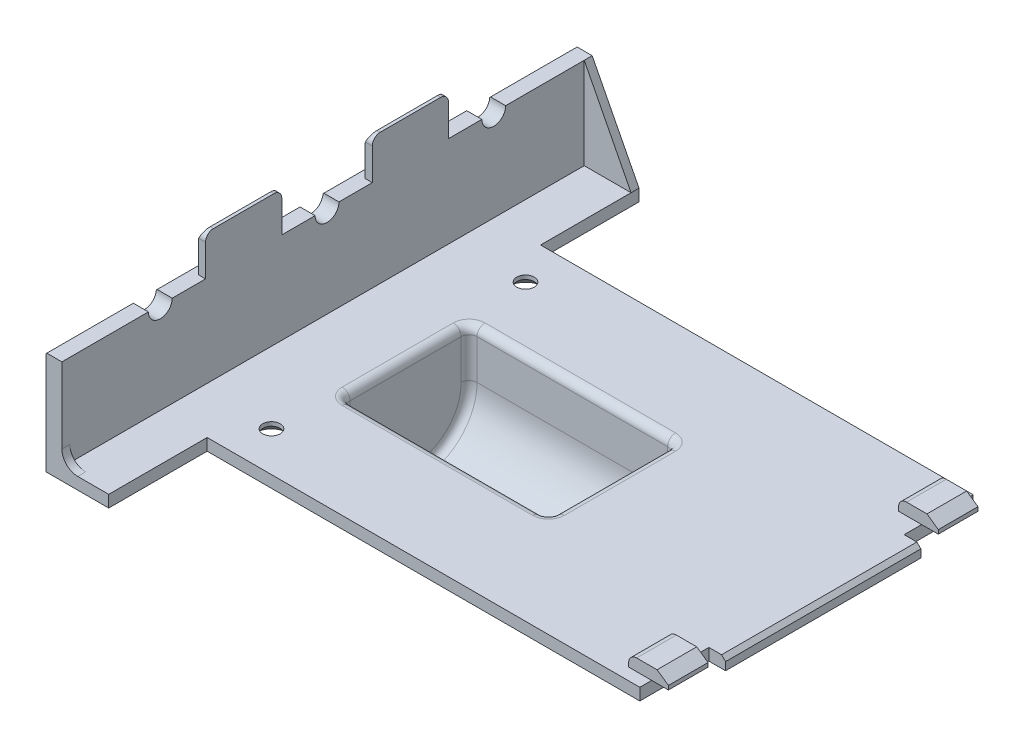
SolidWorks part; units mm, degrees
note: The reader was unsure of these and kept them because the rebuilt part matched: shared geometry of "Sketch4<2>".
material "PE High Density"
ref_plane "Front Plane" through (0, 0, 0) normal (0, 0, 1) x (1, 0, 0)
ref_plane "Top Plane" through (0, 0, 0) normal (0, 1, 0) x (1, 0, 0)
ref_plane "Right Plane" through (0, 0, 0) normal (1, 0, 0) x (0, 0, -1)
sketch "Sketch1" plane through (0, 0, 0) normal (0, 1, 0) x (1, 0, 0)
  line L1 (0, 0) -> (54.5, 0)
  line L2 (0, 0) -> (0, 42)
  line L3 (0, 42) -> (54.5, 42)
  line L4 (54.5, 0) -> (54.5, 42)
  dimension "D1" = 42
  dimension "D2" = 54.5
extrude "Boss-Extrude1" add sketch "Sketch1" along normal blind 1.5
sketch "Sketch2" plane through (0, 0, 0) normal (0, -1, 0) x (-1, 0, 0)
  line L0 (0, 42) -> (0, 0) construction
  line L1 (0, 13) -> (-30, 13)
  line L2 (0, 13) -> (0, 29)
  line L3 (0, 29) -> (-30, 29)
  line L4 (-30, 13) -> (-30, 29)
  line L5 (-54.5, 21) -> (0, 21) construction
  line L7 (-54.5, 0) -> (-54.5, 42) construction
  dimension "D1" = 16
  dimension "D2" = 30
extrude "Cut-Extrude1" cut sketch "Sketch2" against normal up to next
sketch "Sketch3" plane through (0, 0, 0) normal (-1, 0, 0) x (0, 0, 1)
  line L0 (-30, 0) -> (-30, -4.5)
  line L1 (-22, -12.5) -> (-20, -12.5)
  line L2 (-29, 0) -> (-29, -4.5)
  line L3 (-22, -11.5) -> (-20, -11.5)
  line L4 (-13, 0) -> (-13, -4.5)
  line L5 (-12, 0) -> (-12, -4.5)
  line L6 (-30, 0) -> (-29, 0)
  line L7 (-13, 0) -> (-12, 0)
  arc A0 (-20, -11.5) -> (-13, -4.5) centre (-20, -4.5) ccw
  arc A1 (-29, -4.5) -> (-22, -11.5) centre (-22, -4.5) ccw
  arc A2 (-30, -4.5) -> (-22, -12.5) centre (-22, -4.5) ccw
  arc A3 (-20, -12.5) -> (-12, -4.5) centre (-20, -4.5) ccw
  dimension "D1" = 7
  dimension "D2" = 11.5
  dimension "D3" = 1
extrude "Boss-Extrude2" add sketch "Sketch3" against normal up to surface (26 mm away) from offset 4 up to face at (30, 0.75, -21) offset against normal yes
sketch "Sketch4" plane through (30, 0, 0) normal (1, 0, 0) x (0, 0, -1)
  line L3 (30, 0) -> (12, 0)
  line L10 (12, -4.5) -> (12, 0)
  line L11 (22, -12.5) -> (20, -12.5)
  line L12 (30, 0) -> (30, -4.5)
  line L13 (12, -4.5) -> (12, 0)
  line L14 (22, -12.5) -> (20, -12.5)
  line L15 (30, 0) -> (30, -4.5)
  arc A6 (12, -4.5) -> (20, -12.5) centre (20, -4.5) ccw
  arc A7 (22, -12.5) -> (30, -4.5) centre (22, -4.5) ccw
  arc A8 (12, -4.5) -> (20, -12.5) centre (20, -4.5) ccw
  arc A9 (22, -12.5) -> (30, -4.5) centre (22, -4.5) ccw
  dimension "D1" = 0
extrude "Boss-Extrude3" add sketch "Sketch4" along normal blind 1
extrude "Boss-Extrude5" add sketch "Sketch4<2>" against normal blind 1 from vertex at -26
sketch "Sketch4<2>" plane through (30, 0, 0) normal (1, 0, 0) x (0, 0, -1) same geometry as "Sketch4"
fillet "Fillet1" radius 1 10 edges at (30, -1.5, -13) (30, -9.4497, -15.0503) (30, -11.5, -21) (30, -9.4497, -26.9497) (30, -1.5, -29) (4, -2.25, -13) (4, -9.4497, -15.0503) (4, -11.5, -21) (4, -2.25, -29) (4, -9.4497, -26.9497)
fillet "Fillet2" radius 2 10 edges at (31, -2.25, -12) (31, -10.1569, -14.3431) (31, -12.5, -21) (31, -2.25, -30) (31, -10.1569, -27.6569) (3, -2.25, -12) (3, -10.1569, -14.3431) (3, -12.5, -21) (3, -2.25, -30) (3, -10.1569, -27.6569)
sketch "Sketch5" plane through (0, 0, 0) normal (0, 1, 0) x (1, 0, 0)
  line L0 (0, 13) -> (0, 29)
  line L1 (0, 29) -> (5, 29)
  line L2 (0, 13) -> (5, 13)
  line L6 (4, 28) -> (4, 14)
  line L7 (4, 28) -> (4, 14)
  arc A5 (5, 29) -> (4, 28) centre (5, 28) ccw
  arc A6 (4, 14) -> (5, 13) centre (5, 14) ccw
  arc A7 (5, 29) -> (4, 28) centre (5, 28) ccw
  arc A8 (4, 14) -> (5, 13) centre (5, 14) ccw
  dimension "D1" = 0
extrude "Boss-Extrude6" add sketch "Sketch5" along normal up to surface (1.5 mm away) up to face at (22.7414, 1.5, -21)
sketch "Sketch6" plane through (0, 0, 0) normal (0, -1, 0) x (1, 0, 0)
  line L0 (0, -21) -> (-7.9, -21) construction
  line L1 (0, -42) -> (0, 0) construction
  line L3 (-7.9, 12.4) -> (0, 12.4)
  line L4 (-7.9, 12.4) -> (-7.9, -54.4)
  line L5 (-7.9, -54.4) -> (0, -54.4)
  line L6 (0, 12.4) -> (0, -54.4)
  dimension "D1" = 66.8
  dimension "D2" = 7.9
extrude "Boss-Extrude7" add sketch "Sketch6" against normal up to surface (1.5 mm away) up to face at (17, 1.5, -21)
sketch "Sketch7" plane through (0, 1.5, 0) normal (0, 1, 0) x (1, 0, 0)
  line L0 (0, 54.4) -> (-7.9, 54.4) construction
  line L1 (-7.9, -12.4) -> (-5.9, -12.4)
  line L2 (-7.9, -12.4) -> (-7.9, 54.4)
  line L3 (-7.9, 54.4) -> (-5.9, 54.4)
  line L4 (-5.9, -12.4) -> (-5.9, 54.4)
  dimension "D1" = 2
extrude "Boss-Extrude8" add sketch "Sketch7" along normal blind 11.5
sketch "Sketch8" plane through (-7.9, 0, 0) normal (-1, 0, 0) x (0, 0, 1)
  line L0 (-54.4, 13) -> (12.4, 13) construction
  circle A0 centre (-42, 13) radius 1.5
  circle A1 centre (-21, 13) radius 1.5
  circle A2 centre (0, 13) radius 1.5
  arc A3 (-19.5, 13) -> (-22.5, 13) centre (-21, 13) ccw construction
extrude "Cut-Extrude2" cut sketch "Sketch8" against normal up to next
sketch "Sketch9" plane through (0, 13, 0) normal (0, 1, 0) x (1, 0, 0)
  line L0 (-5.9, 22.5) -> (-5.9, 40.5) construction
  line L1 (-5.9, 36.3) -> (-6.8, 36.3)
  line L2 (-5.9, 36.3) -> (-5.9, 26.7)
  line L3 (-5.9, 26.7) -> (-6.8, 26.7)
  line L4 (-6.8, 36.3) -> (-6.8, 26.7)
  line L5 (-5.9, 36.5) -> (-6.9, 36.5) construction
  line L6 (-6.9, 26.5) -> (-5.9, 26.5) construction
  line L7 (-7.9, 21) -> (-5.9, 21) construction
  line L8 (-7.9, 22.5) -> (-7.9, 19.5) construction
  line L9 (-5.9, 19.5) -> (-5.9, 22.5) construction
  line L10 (-6.8, 5.7) -> (-6.8, 15.3)
  line L11 (-5.9, 15.3) -> (-6.8, 15.3)
  line L12 (-5.9, 5.7) -> (-5.9, 15.3)
  line L13 (-5.9, 5.7) -> (-6.8, 5.7)
  dimension "D1" = 0.2
  dimension "D2" = 0.2
  dimension "D3" = 0.9
extrude "Boss-Extrude9" add sketch "Sketch9" along normal blind 5
chamfer "Chamfer1" distance 0.5 angle 65 2 edges at (-6.8, 18, -31.5) (-6.8, 18, -10.5)
fillet "Fillet3" radius 1 4 edges at (-6.1, 18, -5.7) (-6.1, 18, -15.3) (-6.1, 18, -26.7) (-6.1, 18, -36.3)
sketch "Sketch10" plane through (0, 1.5, 0) normal (0, 1, 0) x (1, 0, 0)
  circle A0 centre (3.1, 37) radius 1.1
  circle A1 centre (3.1, 5) radius 1.1
  dimension "D1" = 2.2
extrude "Cut-Extrude3" cut sketch "Sketch10" against normal up to next
sketch "Sketch11" plane through (0, 0, 0) normal (0, -1, 0) x (1, 0, 0)
  line L0 (54.5, 0) -> (54.5, -42) construction
  line L1 (54.5, -8.7) -> (56.6, -8.7)
  line L2 (54.5, -8.7) -> (54.5, -33.3)
  line L3 (54.5, -33.3) -> (56.6, -33.3)
  line L4 (56.6, -8.7) -> (56.6, -33.3)
  line L5 (56.6, -33.5) -> (56.6, -8.5) construction
  line L6 (56.6, -8.5) -> (54.6, -8.5) construction
  line L7 (54.6, -33.5) -> (56.6, -33.5) construction
  dimension "D1" = 0.2
  dimension "D2" = 0.2
extrude "Boss-Extrude10" add sketch "Sketch11" against normal up to surface (1.5 mm away) up to face at (3.1, 1.5, -3.9)
sketch "Sketch12" plane through (0, 0, 12.4) normal (0, 0, 1) x (1, 0, 0)
  line L0 (-5.9, 1.5) -> (0, 1.5)
  line L1 (0, 1.5) -> (-5.9, 13)
  line L2 (-5.9, 13) -> (-5.9, 1.5)
extrude "Boss-Extrude11" add sketch "Sketch12" against normal blind 1
sketch "Sketch13" plane through (0, 0, -54.4) normal (0, 0, -1) x (-1, 0, 0)
  line L0 (5.9, 1.5) -> (5.9, 13)
  line L1 (5.9, 13) -> (0, 1.5)
  line L2 (0, 1.5) -> (5.9, 1.5)
extrude "Boss-Extrude12" add sketch "Sketch13" against normal blind 1
sketch "Sketch14" plane through (0, 1.5, 0) normal (0, 1, 0) x (1, 0, 0)
  line L0 (56.6, 21) -> (30, 21) construction
  line L1 (56.6, 8.7) -> (56.6, 33.3) construction
  line L2 (30, 14) -> (30, 28) construction
  line L4 (51.6, 40.5) -> (56.6, 40.5)
  line L5 (51.6, 40.5) -> (51.6, 35.5)
  line L6 (51.6, 35.5) -> (56.6, 35.5)
  line L7 (56.6, 40.5) -> (56.6, 35.5)
  line L8 (56.6, 1.5) -> (56.6, 6.5)
  line L9 (51.6, 6.5) -> (56.6, 6.5)
  line L10 (51.6, 1.5) -> (51.6, 6.5)
  line L11 (51.6, 1.5) -> (56.6, 1.5)
  dimension "D1" = 5
  dimension "D2" = 5
  dimension "D3" = 29
extrude "Boss-Extrude13" add sketch "Sketch14" along normal blind 1.5
chamfer "Chamfer2" distance 1 angle 55 2 edges at (56.6, 3, -4) (56.6, 3, -38)
fillet "Fillet4" radius 1 2 edges at (51.6, 3, -4) (51.6, 3, -38)
chamfer "Chamfer3" distance 1 angle 45 2 edges at (3.1, 0, -38.1) (3.1, 0, -6.1)
fillet "Fillet5" radius 2 8 edges at (30.4142, 0, -29.4142) (17, 0, -30) (3.5858, 0, -29.4142) (3, 0, -21) (3.5858, 0, -12.5858) (17, 0, -12) (30.4142, 0, -12.5858) (31, 0, -21)
fillet "Fillet6" radius 1 8 edges at (29.7071, 1.5, -13.2929) (17, 1.5, -13) (4.2929, 1.5, -13.2929) (4, 1.5, -21) (4.2929, 1.5, -28.7071) (17, 1.5, -29) (29.7071, 1.5, -28.7071) (30, 1.5, -21)
chamfer "Chamfer4" distance 0.5 angle 45 1 edges at (56.6, 1.5, -21)
chamfer "Chamfer5" distance 0.1 angle 45 4 edges at (-7.9, 13, 6.95) (-7.9, 13, -10.5) (-7.9, 13, -48.95) (-7.9, 13, -31.5)
sketch "Sketch15" plane through (0, 0, 12.4) normal (0, 0, 1) x (1, 0, 0)
  line L0 (-5.9, 13) -> (-5.9, 3.5)
  line L1 (-3.9, 1.5) -> (0, 1.5)
  line L2 (0, 1.5) -> (-5.9, 13) construction
  line L3 (-5.9, 13) -> (0, 1.5)
  line L4 (0, 1.5) -> (54.5, 1.5) construction
  arc A1 (-5.9, 3.5) -> (-3.9, 1.5) centre (-3.9, 3.5) ccw
extrude "Cut-Extrude4" cut sketch "Sketch15" against normal up to next
